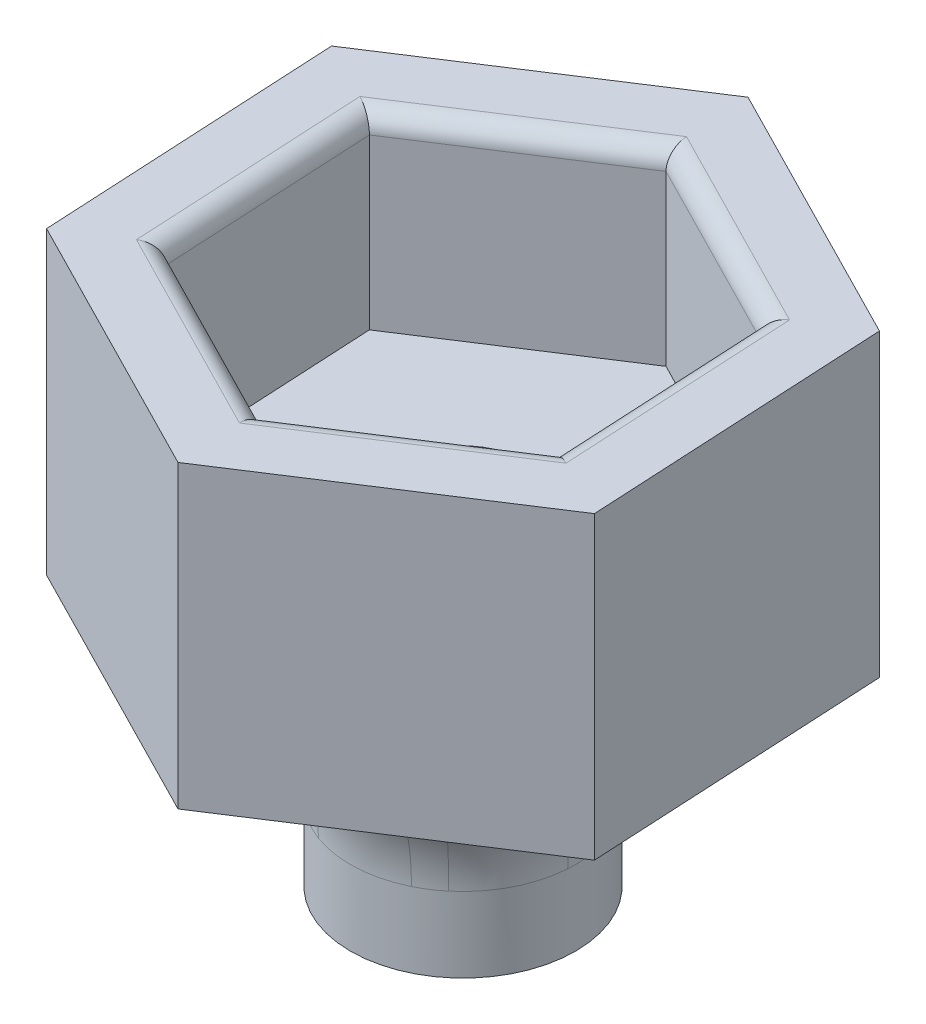
SolidWorks part; units mm, degrees
ref_plane "Front Plane" through (0, 0, 0) normal (0, 0, 1) x (1, 0, 0)
ref_plane "Top Plane" through (0, 0, 0) normal (0, 1, 0) x (1, 0, 0)
ref_plane "Right Plane" through (0, 0, 0) normal (1, 0, 0) x (0, 0, -1)
sketch "Sketch1" plane through (0, 0, 0) normal (0, 1, 0) x (1, 0, 0)
  line L0 (-1.2298, 1.1) -> (1.2298, 1.1)
  circle A0 centre (0, 0) radius 1.65
  circle A1 centre (0, 0) radius 3
  point P5 (0, 1.1)
  dimension "D1" = 3.3
  dimension "D2" = 6
  dimension "D3" = 1.1
extrude "Boss-Extrude1" add sketch "Sketch1" along normal blind 9 contours A1 A0 region at (-2.9151, 0, 0)
sketch "Sketch2" plane through (0, 9, 0) normal (0, 1, 0) x (1, 0, 0)
  line L0 (-0.4172, 8.0143) -> (-7.1492, 3.6459)
  line L1 (-4.7947, -3.1113) -> (0.2971, -5.708)
  line L2 (0.2971, -5.708) -> (5.0919, -2.5967)
  line L3 (5.0919, -2.5967) -> (4.7947, 3.1113)
  line L4 (4.7947, 3.1113) -> (-0.2971, 5.708)
  line L5 (-0.2971, 5.708) -> (-5.0919, 2.5967)
  line L6 (-5.0919, 2.5967) -> (-4.7947, -3.1113)
  line L7 (-7.1492, 3.6459) -> (-6.732, -4.3684)
  line L8 (-6.732, -4.3684) -> (0.4172, -8.0143)
  line L9 (0.4172, -8.0143) -> (7.1492, -3.6459)
  line L10 (7.1492, -3.6459) -> (6.732, 4.3684)
  line L11 (6.732, 4.3684) -> (-0.4172, 8.0143)
  circle A0 centre (0, 0) radius 4.95 construction
  circle M7 centre (0, 0) radius 3
  dimension "D1" = 9.9
  dimension "D2" = 2
extrude "Boss-Extrude2" add sketch "Sketch2" along normal blind 5 separate body
extrude "Boss-Extrude3" add sketch "Sketch2<3>" against normal blind 3 contours L5 L6 L1 L2 L3 L4 M7 | L10 L11 L0 L7 L8 L9 L6 L5 L4 L3 L2 L1 region at (3.0598, 9, -6) region at (-4.7905, 9, 0.2494)
sketch "Sketch2<3>" plane through (0, 9, 0) normal (0, 1, 0) x (1, 0, 0) same geometry as "Sketch2"
fillet "Fillet1" radius 4 1 edges at (0, 6, 3)
fillet "Fillet2" radius 0.5 6 edges at (4.9433, 14, -0.2573) (2.6945, 14, 4.1524) (-2.2488, 14, 4.4097) (2.2488, 14, -4.4097) (-2.6945, 14, -4.1524) (-4.9433, 14, 0.2573)
